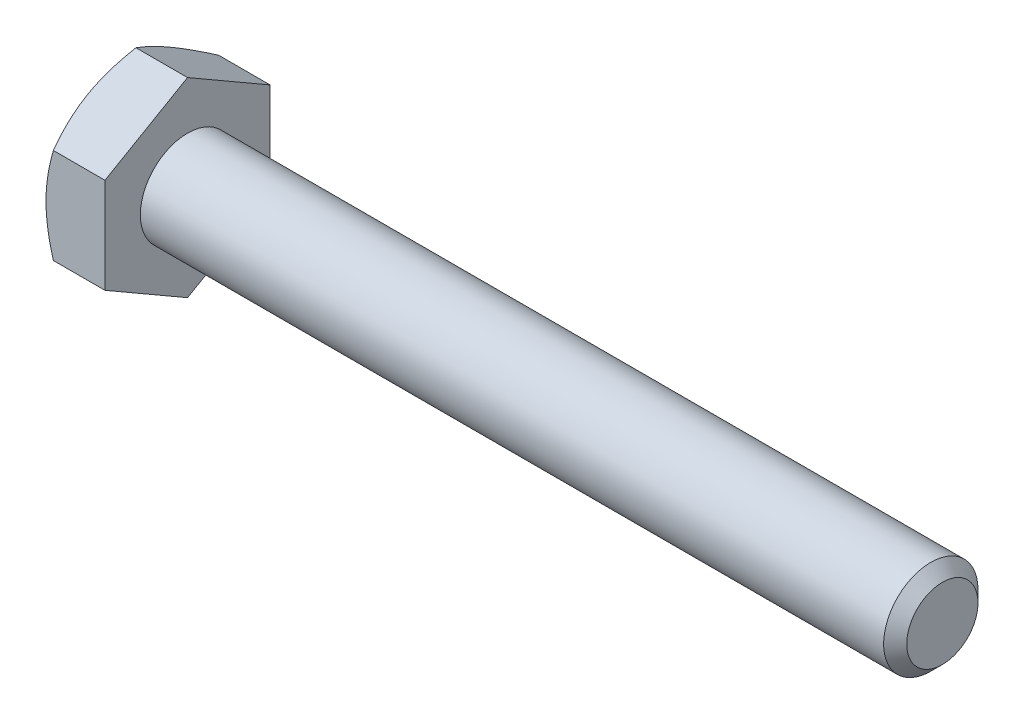
SolidWorks part; units mm, degrees
material "Alloy Steel"
ref_plane "Front Plane" through (0, 0, 0) normal (0, 0, 1) x (1, 0, 0)
ref_plane "Top Plane" through (0, 0, 0) normal (0, 1, 0) x (1, 0, 0)
ref_plane "Right Plane" through (0, 0, 0) normal (1, 0, 0) x (0, 0, -1)
sketch "Sketch1" plane through (0, 0, 0) normal (0, 0, 1) x (1, 0, 0)
  line L0 (-27.3844, 0) -> (27.3844, 0) construction
  line L1 (27.3844, 3.175) -> (27.3844, -3.175) construction
  line L2 (-23.4156, 5.5562) -> (-23.4156, -5.5562) construction
  line L3 (-27.3844, 5.5562) -> (-27.3844, -5.5562) construction
  point P9 (-23.4156, 0)
  point P10 (22.9394, -3.175)
  dimension "D1" = 4.445
  dimension "Screw Dia" = 6.35
  dimension "Hex" = 11.1125
  dimension "Head Ht" = 3.9688
  dimension "Screw Lenght" = 50.8
ref_plane "Plane2" through (27.3844, 0, 0) normal (1, 0, 0) x (0, 0, -1)
sketch "Sketch5" plane through (27.3844, 0, 0) normal (1, 0, 0) x (0, 0, -1)
  circle A0 centre (0, 0) radius 3.175
extrude "Boss-Extrude3" add sketch "Sketch5" against normal up to vertex (50.8 mm away) up to point (-23.4156, 0, 0)
sketch "Sketch9" plane through (27.3844, 0, 0) normal (1, 0, 0) x (0, 0, -1)
  circle A1 centre (0, 0) radius 3.175
  circle A2 centre (0, 0) radius 3.175
  dimension "D1" = 0
curve "Helix/Spiral1" pitch 1.27 height 52.07 turns 41 parameters "Pitch"=1.27
chamfer "Chamfer1" distance 0.7772 angle 45 1 edges at (27.3844, 0, -3.175)
sketch "Sketch10" plane through (0, 0, 0) normal (0, 0, 1) x (1, 0, 0)
  line L0 (27.3844, 3.175) -> (27.8606, 2.3501)
  line L1 (27.8606, 2.3501) -> (28.0194, 2.3501)
  line L2 (28.0194, 2.3501) -> (28.4956, 3.175)
  line L3 (27.3844, 3.175) -> (28.4956, 3.175)
  line L4 (27.94, 3.175) -> (27.94, 2.3501) construction
  line L5 (27.6225, 2.7626) -> (28.2575, 2.7626) construction
  dimension "D1" = 60
  dimension "D2" = 0.1588
  dimension "D3" = 0.635
sketch "Sketch6" plane through (-23.4156, 0, 0) normal (-1, 0, 0) x (0, 0, 1)
  line L0 (0, 5.5562) -> (0, -5.5562) construction
  line L1 (5.5563, 3.2079) -> (0, 6.4158)
  line L2 (0, 6.4158) -> (-5.5562, 3.2079)
  line L3 (-5.5562, 3.2079) -> (-5.5562, -3.2079)
  line L4 (-5.5562, -3.2079) -> (0, -6.4158)
  line L5 (0, -6.4158) -> (5.5563, -3.2079)
  line L6 (5.5563, -3.2079) -> (5.5563, 3.2079)
  circle A0 centre (0, 0) radius 5.5563 construction
extrude "Boss-Extrude4" add sketch "Sketch6" along normal up to vertex (3.9688 mm away) up to point (-27.3844, -5.5562, 0)
sketch "Sketch7" plane through (-27.3844, 0, 0) normal (-1, 0, 0) x (0, 0, 1)
  circle A0 centre (0, 0) radius 5.5563 construction
  circle A1 centre (0, 0) radius 5.5563
sketch "Sketch8" plane through (-27.3844, 0, 0) normal (-1, 0, 0) x (0, 0, 1)
  circle A0 centre (0, 0) radius 5.5563 construction
  circle A1 centre (0, 0) radius 5.5563
extrude "Cut-Extrude3" cut sketch "Sketch8" against normal through all draft 60 flip side to cut
sketch "Sketch12" plane through (-27.3844, 0, 0) normal (-1, 0, 0) x (0, 0, 1)
  line L0 (0, 4.2783) -> (0, 2.3892) construction
  line L1 (0.1667, 4.2783) -> (0.1667, 2.3892)
  line L2 (-0.1667, 4.2783) -> (-0.1667, 2.3892)
  line L3 (0, 3.175) -> (0, -3.175) construction
  arc A0 (0.1667, 4.2783) -> (-0.1667, 4.2783) centre (0, 4.2783) ccw
  arc A1 (-0.1667, 2.3892) -> (0.1667, 2.3892) centre (0, 2.3892) ccw
  circle A3 centre (0, 0) radius 2.2225 construction
  circle A4 centre (0, 0) radius 4.445 construction
  point P2 (0, 3.3337)
  dimension "D1" = 4.445
  dimension "D3" = 8.89
  dimension "D2" = 0.3334
extrude "Cut-Extrude4" cut sketch "Sketch12" against normal blind 0.254
pattern_circular "CirPattern1" count 3 over 360 about axis through (-23.4156, 0, 0) along (1, 0, 0) of "Cut-Extrude4"
equation "\"D2@Sketch10\" = \"Pitch@Helix/Spiral1\"*.125"
equation "\"D3@Sketch10\" = \"Pitch@Helix/Spiral1\"*.5"
equation "\"D1@Chamfer1\" = \"Pitch@Helix/Spiral1\"*.612"
equation "\"D1@Sketch12\" = \"Hex@Sketch1\"*.4"
equation "\"D3@Sketch12\" = \"Hex@Sketch1\"*.8"
equation "\"D2@Sketch12\" = \"Hex@Sketch1\"*.03"
equation "\"D1@Sketch1\" = \"Pitch@Helix/Spiral1\"*3.5"
equation "\"D3@Helix/Spiral1\" = \"Screw Lenght@Sketch1\"+\"Pitch@Helix/Spiral1\""
